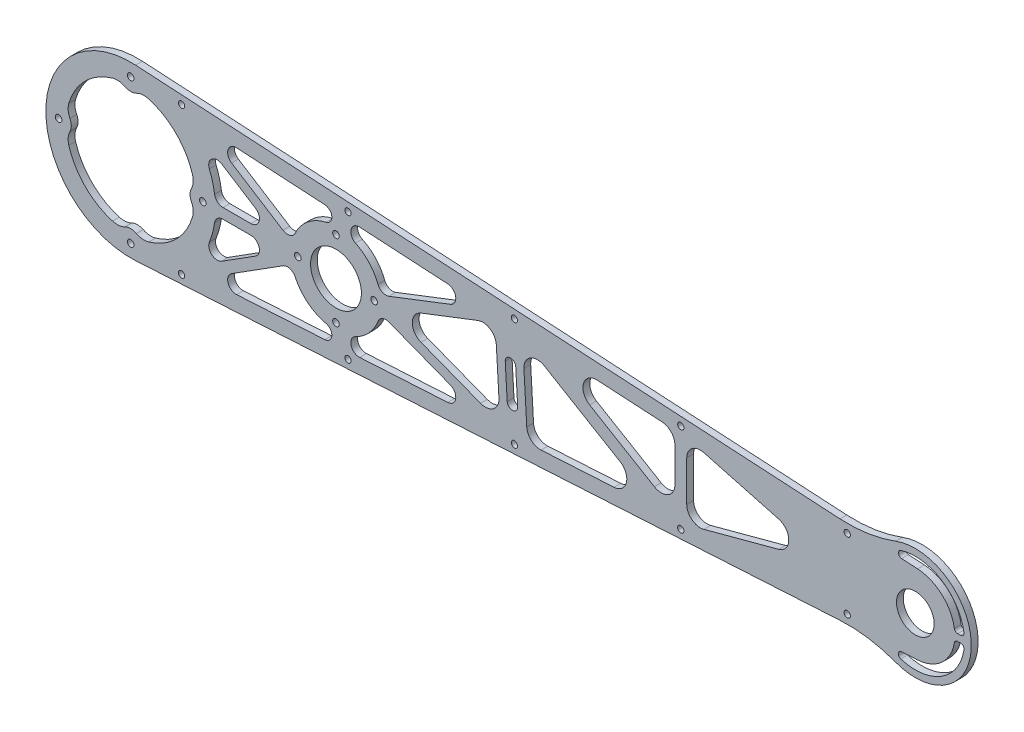
SolidWorks part; units mm, degrees
material "Thornel VCB-20 Carbon Cloth"
ref_plane "Front Plane" through (0, 0, 0) normal (0, 0, 1) x (1, 0, 0)
ref_plane "Top Plane" through (0, 0, 0) normal (0, 1, 0) x (1, 0, 0)
ref_plane "Right Plane" through (0, 0, 0) normal (1, 0, 0) x (0, 0, -1)
sketch "Sketch1" plane through (0, 0, 0) normal (0, 0, 1) x (1, 0, 0)
  line L0 (-231.25, 0) -> (231.25, 0) construction
  line L1 (-228.3622, 49.9165) -> (232.595, 23.2486)
  line L2 (-228.3622, -49.9165) -> (232.595, -23.2486)
  line L3 (191.094, 20.6412) -> (-201.25, 43.3396) construction
  line L4 (-103.164, -37.665) -> (-5.078, -31.9904) construction
  circle A0 centre (231.25, 0) radius 11.1125
  arc A1 (232.595, 23.2486) -> (232.595, -23.2486) centre (231.25, 0) cw
  circle A2 centre (-231.25, 0) radius 42.5 construction
  circle A3 centre (-110.25, 0) radius 22.5 construction
  arc A4 (-228.3622, 49.9165) -> (-228.3622, -49.9165) centre (-231.25, 0) ccw
  circle A5 centre (-231.25, 42.5) radius 1.75 construction
  circle A6 centre (-231.25, 0) radius 30
  circle A7 centre (-110.25, 0) radius 15
  circle A8 centre (231.25, 0) radius 35.306 construction
  circle A9 centre (-201.25, 43.3396) radius 1.85
  circle A10 centre (-103.164, 37.665) radius 1.85
  circle A11 centre (-5.078, 31.9904) radius 1.85
  circle A12 centre (93.008, 26.3158) radius 1.85
  circle A13 centre (191.094, 20.6412) radius 1.85
  circle A14 centre (289.1799, 14.9666) radius 1.85 construction
  circle A15 centre (191.094, -20.6412) radius 1.85
  circle A16 centre (93.008, -26.3158) radius 1.85
  circle A17 centre (-5.078, -31.9904) radius 1.85
  circle A18 centre (-103.164, -37.665) radius 1.85
  circle A19 centre (-201.25, -43.3396) radius 1.85
  point P4 (0, 0)
  point P15 (-231.25, 44.25)
  point P16 (-273.75, 0)
  point P17 (-231.25, 50)
  point P18 (-110.25, 22.5)
  point P19 (-231.25, -42.5)
  point P20 (-188.75, 0)
  point P21 (-132.75, 0)
  point P22 (-110.25, -22.5)
  point P23 (-87.75, 0)
  dimension "D2" = 22.225
  dimension "D3" = 85
  dimension "D5" = 45
  dimension "D6" = 3.5
  dimension "D7" = 7.5
  dimension "D9" = 60
  dimension "D10" = 30
  dimension "D11" = 70.612
  dimension "D13" = 3.7
  dimension "D16" = 6
  dimension "D1" = 462.5
  dimension "D4" = 121
  dimension "D12" = 5
  dimension "D14" = 30
  dimension "D17" = 393
extrude "Boss-Extrude1" add sketch "Sketch1" along normal blind 4
sketch "Sketch4" plane through (0, 0, 4) normal (0, 0, 1) x (1, 0, 0)
  point P0 (-231.25, 42.5)
  point P7 (-188.75, 0)
  point P10 (-132.75, 0)
  point P13 (-110.25, 22.5)
  point P16 (-87.75, 0)
  point P19 (-110.25, -22.5)
  point P24 (-273.75, 0)
  point P28 (-231.25, -42.5)
hole_wizard "M3.5 Clearance Hole1" positions "Sketch4" profile "Sketch6" hole size "M3.5" standard "ANSI Metric" end condition up to next
sketch "Sketch6" plane through (-231.25, 42.5, 4) normal (1, 0, 0) x (0, -1, 0)
  line L0 (0, 0) -> (0, 4)
  line L1 (0, 4) -> (1.95, 4)
  line L2 (1.95, 4) -> (1.95, 0)
  line L5 (1.95, 0) -> (0, 0)
  line L11 (0, -6.35) -> (0, 107.95) construction
  dimension "Thru Hole Dia." = 3.9
  dimension "Thru Hole Depth" = 4
sketch "Sketch7" plane through (0, 0, 4) normal (0, 0, 1) x (1, 0, 0)
  line L0 (93.008, 26.3158) -> (93.008, -26.3158) construction
  line L1 (93.008, -26.3158) -> (191.094, 0) construction
  line L2 (191.094, 0) -> (93.008, 26.3158) construction
  line L3 (191.094, 0) -> (-87.75, 0) construction
  line L4 (191.094, -20.6412) -> (191.094, 20.6412) construction
  line L5 (106.581, 19.5682) -> (150.7172, 7.7267)
  line L6 (150.7172, -7.7267) -> (106.581, -19.5682)
  line L7 (96.508, -11.8414) -> (96.508, 11.8414)
  line L8 (-5.078, -31.9904) -> (-9.0827, 37.2305) construction
  line L9 (-5.078, 31.9904) -> (93.008, -26.3158) construction
  line L10 (-5.078, 31.9904) -> (93.008, 26.3158) construction
  line L11 (-5.078, -31.9904) -> (93.008, -26.3158) construction
  line L12 (-87.75, 0) -> (-103.164, 37.665) construction
  line L13 (-103.164, 37.665) -> (-5.078, 31.9904) construction
  line L14 (-5.078, 31.9904) -> (-87.75, 0) construction
  line L15 (89.508, -5.5197) -> (89.508, 14.9611)
  line L16 (81.97, 22.9477) -> (43.8014, 25.1559)
  line L17 (39.2515, 10.2925) -> (77.4201, -12.3965)
  line L18 (12.6104, 16.8224) -> (57.2669, -9.7233)
  line L19 (53.6411, -24.5867) -> (10.6642, -27.073)
  line L20 (2.2155, -19.5484) -> (0.5359, 9.4836)
  line L21 (232.595, 23.2486) -> (-228.3622, 49.9165) construction
  line L22 (-228.3622, -49.9165) -> (232.595, -23.2486) construction
  line L23 (-14.1831, -13.1198) -> (-15.7202, 13.4491)
  line L24 (-26.5939, 20.448) -> (-60.156, 7.4609)
  line L25 (-60.156, -7.4609) -> (-25.0568, -21.0428)
  line L27 (-79.0253, 6.5929) -> (-42.8256, 20.6005)
  line L28 (-44.3412, 30.2553) -> (-96.2601, 33.2589)
  line L32 (-132.75, 0) -> (-188.75, 0) construction
  line L33 (-188.75, 0) -> (-201.25, 43.3396) construction
  line L34 (-201.25, 43.3396) -> (-132.75, 0) construction
  line L35 (-132.75, 0) -> (-103.164, 37.665) construction
  line L36 (-103.164, 37.665) -> (-201.25, 43.3396) construction
  line L37 (-171.7722, 28.2392) -> (-141.4788, 9.0727)
  line L39 (-116.7705, 34.4455) -> (-168.8101, 37.4562)
  line L41 (-176.8349, 3) -> (-160.3569, 3)
  line L42 (-157.6835, 12.2253) -> (-177.574, 24.8099)
  line L44 (-116.7705, -34.4455) -> (-168.8101, -37.4562)
  line L45 (-171.7722, -28.2392) -> (-141.4788, -9.0727)
  line L46 (-157.6835, -12.2253) -> (-177.574, -24.8099)
  line L48 (-176.8349, -3) -> (-160.3569, -3)
  line L50 (-44.3412, -30.2553) -> (-96.2601, -33.2589)
  line L51 (-79.0253, -6.5929) -> (-42.8256, -20.6005)
  line L52 (-103.164, -37.665) -> (-110.25, -22.5) construction
  line L53 (-113.0786, -28.2577) -> (-106.259, -42.8525) construction
  line L54 (-101.0351, -30.41) -> (-95.5118, -42.2307) construction
  line L55 (-6.2272, -12.127) -> (-7.3823, 7.8396) construction
  line L56 (-9.322, -12.306) -> (-10.4771, 7.6606)
  line L57 (-3.1324, -11.9479) -> (-4.2875, 8.0187)
  arc A0 (150.7172, 7.7267) -> (150.7172, -7.7267) centre (148.6441, 0) cw
  arc A1 (106.581, -19.5682) -> (96.508, -11.8414) centre (104.508, -11.8414) cw
  arc A2 (106.581, 19.5682) -> (96.508, 11.8414) centre (104.508, 11.8414) ccw
  arc A3 (89.508, 14.9611) -> (81.97, 22.9477) centre (81.508, 14.9611) ccw
  arc A4 (43.8014, 25.1559) -> (39.2515, 10.2925) centre (43.3394, 17.1693) ccw
  arc A5 (89.508, -5.5197) -> (77.4201, -12.3965) centre (81.508, -5.5197) cw
  arc A6 (57.2669, -9.7233) -> (53.6411, -24.5867) centre (53.1791, -16.6) cw
  arc A7 (10.6642, -27.073) -> (2.2155, -19.5484) centre (10.2022, -19.0864) cw
  arc A8 (12.6104, 16.8224) -> (0.5359, 9.4836) centre (8.5226, 9.9456) ccw
  arc A9 (-14.1831, -13.1198) -> (-25.0568, -21.0428) centre (-22.1698, -13.5819) cw
  arc A10 (-15.7202, 13.4491) -> (-26.5939, 20.448) centre (-23.7069, 12.9871) ccw
  arc A11 (-60.156, 7.4609) -> (-60.156, -7.4609) centre (-57.269, 0) ccw
  arc A12 (-42.8256, 20.6005) -> (-44.3412, 30.2553) centre (-44.63, 25.2636) ccw
  arc A18 (-171.7722, 28.2392) -> (-168.8101, 37.4562) centre (-169.0989, 32.4645) cw
  arc A21 (-160.3569, 3) -> (-157.6835, 12.2253) centre (-160.3569, 8) ccw
  arc A22 (-181.7818, 7.2727) -> (-176.8349, 3) centre (-176.8349, 8) ccw
  arc A23 (-184.8839, 18.7133) -> (-177.574, 24.8099) centre (-180.2473, 20.5846) cw
  arc A26 (-171.7722, -28.2392) -> (-168.8101, -37.4562) centre (-169.0989, -32.4645) ccw
  arc A27 (-184.8839, -18.7133) -> (-177.574, -24.8099) centre (-180.2473, -20.5846) ccw
  arc A28 (-181.7818, -7.2727) -> (-176.8349, -3) centre (-176.8349, -8) cw
  arc A29 (-160.3569, -3) -> (-157.6835, -12.2253) centre (-160.3569, -8) cw
  circle A30 centre (-110.25, 0) radius 15 construction
  circle A31 centre (-110.25, 0) radius 15 construction
  circle A32 centre (-110.25, 0) radius 22.5 construction
  arc A34 (-85.4996, 9.4693) -> (-98.7049, 23.8529) centre (-110.25, 0) ccw
  arc A37 (-85.4996, 9.4693) -> (-79.0253, 6.5929) centre (-80.8297, 11.2559) ccw
  arc A38 (-42.8256, -20.6005) -> (-44.3412, -30.2553) centre (-44.63, -25.2636) cw
  arc A39 (-96.2601, -33.2589) -> (-98.7049, -23.8529) centre (-96.5463, -28.3126) cw
  arc A40 (-134.2728, 11.1872) -> (-116.0666, 25.8538) centre (-110.25, 0) cw
  arc A41 (-85.4996, -9.4693) -> (-98.7049, -23.8529) centre (-110.25, 0) cw
  arc A42 (-85.4996, -9.4693) -> (-79.0253, -6.5929) centre (-80.8297, -11.2559) cw
  arc A43 (-116.7705, 34.4455) -> (-116.0666, 25.8538) centre (-117.0219, 30.1002) cw
  arc A44 (-134.2728, 11.1872) -> (-141.4788, 9.0727) centre (-138.8054, 13.298) cw
  arc A45 (-116.7705, -34.4455) -> (-116.0666, -25.8538) centre (-117.0219, -30.1002) ccw
  arc A46 (-134.2728, -11.1872) -> (-116.0666, -25.8538) centre (-110.25, 0) ccw
  arc A47 (-134.2728, -11.1872) -> (-141.4788, -9.0727) centre (-138.8054, -13.298) ccw
  arc A48 (-96.2601, 33.2589) -> (-98.7049, 23.8529) centre (-96.5463, 28.3126) ccw
  circle A49 centre (-5.078, -31.9904) radius 1.85 construction
  circle A50 centre (-5.078, -31.9904) radius 1.85
  arc A51 (-184.8839, 18.7133) -> (-181.7818, 7.2727) centre (-231.25, 0) cw
  arc A52 (-228.3622, 49.9165) -> (-228.3622, -49.9165) centre (-231.25, 0) ccw construction
  arc A53 (-228.3622, 49.9165) -> (-228.3622, -49.9165) centre (-231.25, 0) ccw
  arc A55 (-184.8839, -18.7133) -> (-181.7818, -7.2727) centre (-231.25, 0) ccw
  arc A56 (-9.322, -12.306) -> (-3.1324, -11.9479) centre (-6.2272, -12.127) ccw
  arc A57 (-4.2875, 8.0187) -> (-10.4771, 7.6606) centre (-7.3823, 7.8396) ccw
  point P36 (179.5167, 0)
  point P59 (-79.437, 0)
  point P102 (-113.0786, -28.2577)
  point P126 (-6.8048, -2.1437)
  dimension "D8" = 8
  dimension "D11" = 5
  dimension "D12" = 5
  dimension "D18" = 5
  dimension "D19" = 5
  dimension "D20" = 3.1
  dimension "D10" = 4
  dimension "D21" = 5
  dimension "D1" = 3
  dimension "D2" = 7
  dimension "D3" = 8
  dimension "D4" = 8
  dimension "D5" = 8
  dimension "D6" = 16
  dimension "D7" = 6
  dimension "D9" = 8
  dimension "D13" = 8
  dimension "D14" = 5
  dimension "D15" = 6
  dimension "D16" = 24.8967
  dimension "D17" = 6
  dimension "D22" = 20
extrude "Cut-Extrude1" cut sketch "Sketch7" against normal blind 10 contours A55 A27 L46 A29 L48 A28 | A23 A51 A22 L41 A21 L42 | A44 A40 A43 L39 A18 L37 | A46 A47 L45 A26 L44 A45 | A42 A41 A39 L50 A38 L51 | L28 A48 A34 A37 L27 A12 | L24 A11 L25 A9 L23 A10 | L18 A8 L20 A7 L19 A6 | L5 A2 L7 A1 L6 A0 | A5 L15 A3 L16 A4 L17 | L57 A57 L56 A56 region at (121.2449, 0, 4) region at (66.798, 9.2025, 4) region at (25.4746, -8.5651, 4) region at (-35.249, -0.2844, 4) region at (-71.8834, 22.3672, 4) region at (-143.7532, 26.2538, 4) region at (-171.7996, 12.3824, 4) region at (-143.7532, -26.2538, 4) region at (-171.7996, -12.3824, 4) region at (-71.8834, -22.3672, 4) region at (-6.8048, -2.1437, 4)
sketch "Sketch8" plane through (0, 0, 4) normal (0, 0, 1) x (1, 0, 0)
  arc A0 (-267.0517, -3.3738) -> (-267.0517, 3.3738) centre (-273.75, 0) ccw
  arc A1 (-267.7172, 10.6837) -> (-241.9337, 36.4672) centre (-231.25, 0) cw
  arc A2 (-228.3622, 49.9165) -> (-228.3622, -49.9165) centre (-231.25, 0) ccw construction
  arc A3 (-228.3622, 49.9165) -> (-228.3622, -49.9165) centre (-231.25, 0) ccw
  circle A4 centre (-273.75, 0) radius 1.95 construction
  circle A5 centre (-273.75, 0) radius 1.95
  arc A6 (-234.6238, 35.8017) -> (-227.8762, 35.8017) centre (-231.25, 42.5) ccw
  arc A7 (-220.5663, 36.4672) -> (-194.7828, 10.6837) centre (-231.25, 0) cw
  arc A8 (-195.4483, 3.3738) -> (-195.4483, -3.3738) centre (-188.75, 0) ccw
  arc A9 (-194.7828, -10.6837) -> (-220.5663, -36.4672) centre (-231.25, 0) cw
  arc A10 (-227.8762, -35.8017) -> (-234.6238, -35.8017) centre (-231.25, -42.5) ccw
  arc A11 (-241.9337, -36.4672) -> (-267.7172, -10.6837) centre (-231.25, 0) cw
  arc A12 (-241.9337, 36.4672) -> (-234.6238, 35.8017) centre (-239.1222, 26.8706) cw
  arc A13 (-227.8762, 35.8017) -> (-220.5663, 36.4672) centre (-223.3778, 26.8706) cw
  arc A14 (-194.7828, 10.6837) -> (-195.4483, 3.3738) centre (-204.3794, 7.8722) cw
  arc A15 (-195.4483, -3.3738) -> (-194.7828, -10.6837) centre (-204.3794, -7.8722) cw
  arc A16 (-220.5663, -36.4672) -> (-227.8762, -35.8017) centre (-223.3778, -26.8706) cw
  arc A17 (-234.6238, -35.8017) -> (-241.9337, -36.4672) centre (-239.1222, -26.8706) cw
  arc A18 (-267.0517, -3.3738) -> (-267.7172, -10.6837) centre (-258.1206, -7.8722) ccw
  arc A19 (-267.0517, 3.3738) -> (-267.7172, 10.6837) centre (-258.1206, 7.8722) cw
  point P24 (-231.25, 0)
  dimension "D1" = 12
  dimension "D3" = 10
  dimension "D2" = 4
extrude "Cut-Extrude2" cut sketch "Sketch8" against normal blind 10 contours A11 A10 A9 A8 A7 A6 A1 A0 region at (-231.25, 0, 4)
sketch "Sketch9" plane through (0, 0, 4) normal (0, 0, 1) x (1, 0, 0)
  line L2 (232.595, 23.2486) -> (-228.3622, 49.9165) construction
  line L3 (-228.3622, -49.9165) -> (232.595, -23.2486) construction
  line L4 (254.5375, 0) -> (264.25, 0) construction
  line L5 (254.4515, 2) -> (260.181, 2)
  line L6 (254.4515, -2) -> (260.181, -2)
  line L7 (215.3411, 24.2468) -> (209.2526, 24.5991)
  line L8 (215.3411, -24.2468) -> (209.2526, -24.5991)
  arc A1 (209.2526, -24.5991) -> (209.2526, 24.5991) centre (231.25, 0) ccw
  arc A2 (232.595, -23.2486) -> (232.595, 23.2486) centre (231.25, 0) ccw construction
  arc A3 (254.4515, -2) -> (254.4515, 2) centre (231.25, 0) ccw
  arc A4 (215.3411, 24.2468) -> (260.181, 2) centre (231.25, 0) cw
  arc A5 (260.181, -2) -> (215.3411, -24.2468) centre (231.25, 0) cw
  dimension "D1" = 33
  dimension "D2" = 4
  dimension "D3" = 4
extrude "Boss-Extrude2" add sketch "Sketch9" against normal up to surface (4 mm away) up to face at (118.288, 0, 0)
fillet "Fillet1" radius 2 6 edges at (215.3411, -24.2468, 2) (254.4515, -2, 2) (260.181, -2, 2) (254.4515, 2, 2) (260.181, 2, 2) (215.3411, 24.2468, 2)
fillet "Fillet2" radius 80 2 edges at (209.2526, 24.5991, 2) (209.2526, -24.5991, 2)
